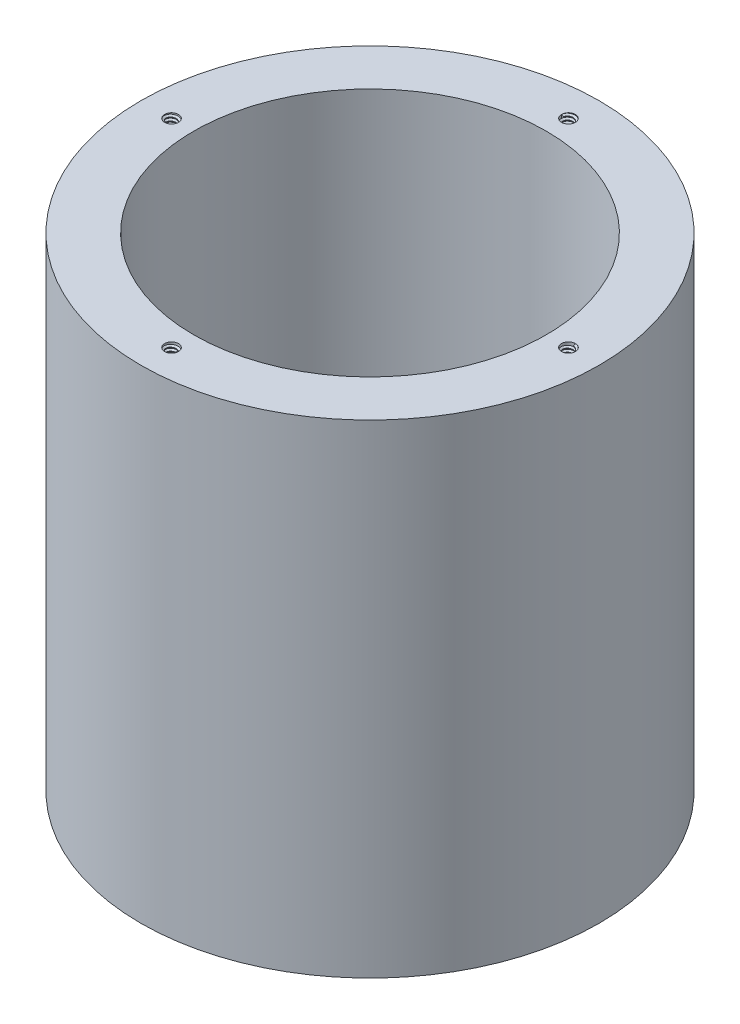
SolidWorks part; units mm, degrees
material "1060 Alloy"
ref_plane "Front Plane" through (0, 0, 0) normal (0, 0, 1) x (1, 0, 0)
ref_plane "Top Plane" through (0, 0, 0) normal (0, 1, 0) x (1, 0, 0)
ref_plane "Right Plane" through (0, 0, 0) normal (1, 0, 0) x (0, 0, -1)
sketch "Sketch1" plane through (0, 0, 0) normal (0, 1, 0) x (1, 0, 0)
  circle A0 centre (0, 0) radius 16.5
  circle A1 centre (0, 0) radius 12.7
  dimension "D1" = 33
  dimension "D2" = 25.4
extrude "Boss-Extrude1" add sketch "Sketch1" along normal blind 34.8
sketch "Sketch2" plane through (0, 34.8, 0) normal (0, 1, 0) x (1, 0, 0)
  circle A0 centre (0, 14.29) radius 0.5
  circle A2 centre (0, 0) radius 12.7 construction
  dimension "D1" = 1
  dimension "D2" = 14.29
extrude "Cut-Extrude1" cut sketch "Sketch2" against normal blind 2
thread "Thread1" pitch 0.25 method extrude profile "Thread Profile1" start angle 0, offset 0, length 2, pitch 0.25, diameter 1
ref_plane "Plane1" through (-0.5, 34.8, -14.29) normal (0, 0, 1) x (-1, 0, 0)
sketch "Thread Profile1" plane through (-0.5, 34.8, -14.29) normal (0, 0, 1) x (-1, 0, 0)
  line L0 (0, 0) -> (0, 0.25) construction
  line L11 (0, 0) -> (0, 0.2187)
  line L12 (0, 0.2187) -> (-0.1353, 0.1406)
  line L13 (-0.1353, 0.1406) -> (-0.1353, 0.0781)
  line L15 (-0.1353, 0.0781) -> (0, 0)
  line L17 (-0.1353, 0.1094) -> (0, 0.1094) construction
  point P2 (0, 0)
  dimension "Pitch" = 0.25
  dimension "Profile_Angle" = 60
  dimension "Profile_Land" = 0.0625
  dimension "Profile_Height" = 0.1353
pattern_circular "CirPattern1" count 4 over 360 about axis through (0, 34.8, 0) along (0, 1, 0) of "Cut-Extrude1", "Thread1"
sketch "Sketch5" plane through (0, 0, 0) normal (0, -1, 0) x (1, 0, 0)
  circle A0 centre (0, 14.29) radius 0.5
  dimension "D1" = 1
  dimension "D2" = 14.29
extrude "Cut-Extrude2" cut sketch "Sketch5" against normal blind 2
thread "Thread2" pitch 0.25 method extrude profile "Thread Profile2" start angle 0, offset 0, length 2, pitch 0.25, diameter 1
ref_plane "Plane2" through (0.5, 0, 14.29) normal (0, 0, 1) x (1, 0, 0)
sketch "Thread Profile2" plane through (0.5, 0, 14.29) normal (0, 0, 1) x (1, 0, 0)
  line L0 (0, 0) -> (0, 0.25) construction
  line L11 (0, 0) -> (0, 0.2187)
  line L12 (0, 0.2187) -> (-0.1353, 0.1406)
  line L13 (-0.1353, 0.1406) -> (-0.1353, 0.0781)
  line L15 (-0.1353, 0.0781) -> (0, 0)
  line L17 (-0.1353, 0.1094) -> (0, 0.1094) construction
  point P2 (0, 0)
  dimension "Pitch" = 0.25
  dimension "Profile_Angle" = 60
  dimension "Profile_Land" = 0.0625
  dimension "Profile_Height" = 0.1353
pattern_circular "CirPattern2" count 4 over 360 about axis through (0, 0, 0) along (0, 1, 0) of "Cut-Extrude2", "Thread2"
